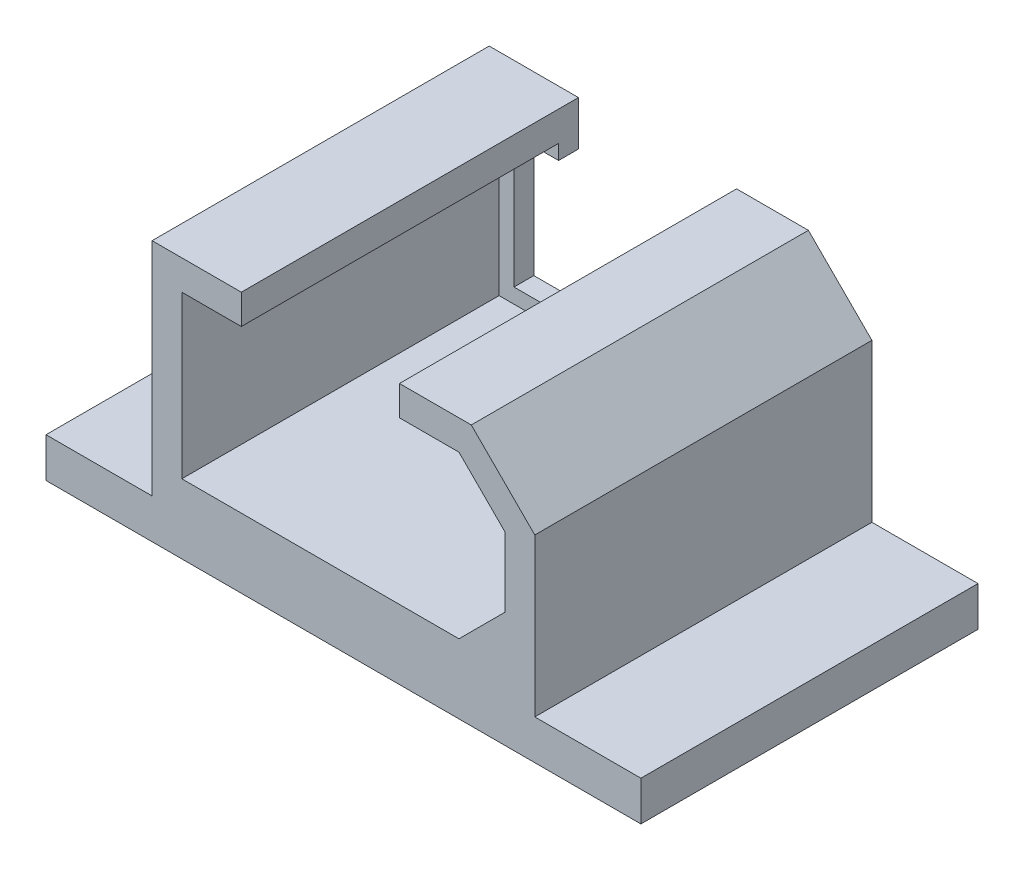
SolidWorks part; units mm, degrees
ref_plane "Спереди" through (0, 0, 0) normal (0, 0, 1) x (1, 0, 0)
ref_plane "Сверху" through (0, 0, 0) normal (0, 1, 0) x (1, 0, 0)
ref_plane "Справа" through (0, 0, 0) normal (1, 0, 0) x (0, 0, -1)
sketch "Эскиз с торца держателя розетки для аккумулятора" plane through (0, 0, 0) normal (0, 0, 1) x (1, 0, 0)
  line L14 (5.35, 13.15) -> (5.35, 2)
  line L28 (24.65, 9.9463) -> (21.4463, 13.15)
  line L32 (5.35, 13.15) -> (9.85, 13.15)
  line L33 (9.85, 13.15) -> (9.85, 11.65)
  line L34 (6.85, 11.65) -> (9.85, 11.65)
  line L35 (24.65, 9.9463) -> (22.6781, 11.9182) construction
  line L36 (6.85, 11.65) -> (6.85, 3.5)
  line L37 (6.85, 3.5) -> (20.825, 3.5)
  line L38 (20.825, 3.5) -> (23.15, 5.825)
  line L39 (23.15, 5.825) -> (23.15, 9.325)
  line L40 (23.15, 9.325) -> (20.825, 11.65)
  line L41 (6.85, 11.65) -> (8.35, 11.65) construction
  line L42 (8.35, 11.65) -> (8.35, 11.65) construction
  line L44 (23.15, 9.325) -> (21.6174, 10.8576) construction
  line L45 (21.4463, 13.15) -> (17.825, 13.15)
  line L46 (17.825, 13.15) -> (17.825, 11.65)
  line L47 (17.825, 11.65) -> (20.825, 11.65)
  line L48 (17.825, 10.9) -> (20.5143, 10.9)
  line L49 (22.4, 9.0143) -> (20.5143, 10.9)
  line L50 (22.4, 6.1357) -> (22.4, 9.0143)
  line L51 (20.5143, 4.25) -> (22.4, 6.1357)
  line L52 (7.6, 4.25) -> (20.5143, 4.25)
  line L53 (7.6, 10.9) -> (7.6, 4.25)
  line L54 (7.6, 10.9) -> (9.85, 10.9)
  line L55 (9.85, 11.65) -> (9.85, 10.9)
  line L56 (17.825, 11.65) -> (17.825, 10.9)
  line L57 (5.35, 2) -> (21.4463, 2) construction
  line L58 (24.65, 2) -> (30, 2)
  line L59 (30, 2) -> (30, 0)
  line L60 (30, 0) -> (0, 0)
  line L61 (0, 0) -> (0, 2)
  line L62 (0, 2) -> (5.35, 2)
  line L63 (24.65, 9.9463) -> (24.65, 2)
  line L64 (21.4463, 2) -> (24.65, 5.2037) construction
  line L65 (24.65, 5.2037) -> (24.65, 9.9463) construction
  point P10 (0, 0)
  point P17 (6.85, 7.575)
  point P18 (23.15, 7.575)
  dimension "D2" = 8.15
  dimension "D3" = 1.5
  dimension "D4" = 16.3
  dimension "D5" = 3.5
  dimension "D6" = 45
  dimension "D7" = 3
  dimension "D8" = 45
  dimension "D9" = 0.75
  dimension "D10" = 2
  dimension "D11" = 30
  dimension "D1" = 1.5
extrude "Держатель розетки для аккумулятора" add sketch "Эскиз с торца держателя розетки для аккумулятора" along normal blind 17 contours L46 L47 L40 L39 L38 L37 L36 L34 L33 L32 L14 L28 L45 region at (7.6, 12.8224, 0)
extrude "Выступ-упор держателя" add sketch "Эскиз1<6>" along normal blind 1 contours L47 L56 L48 L49 L50 L51 L52 L53 L54 L55 L34 L36 L37 L38 L39 L40 region at (9.6678, 11.275, 0)
sketch "Эскиз1<6>" plane through (0, 0, 0) normal (0, 0, 1) x (1, 0, 0) same geometry as "Эскиз с торца держателя розетки для аккумулятора"
